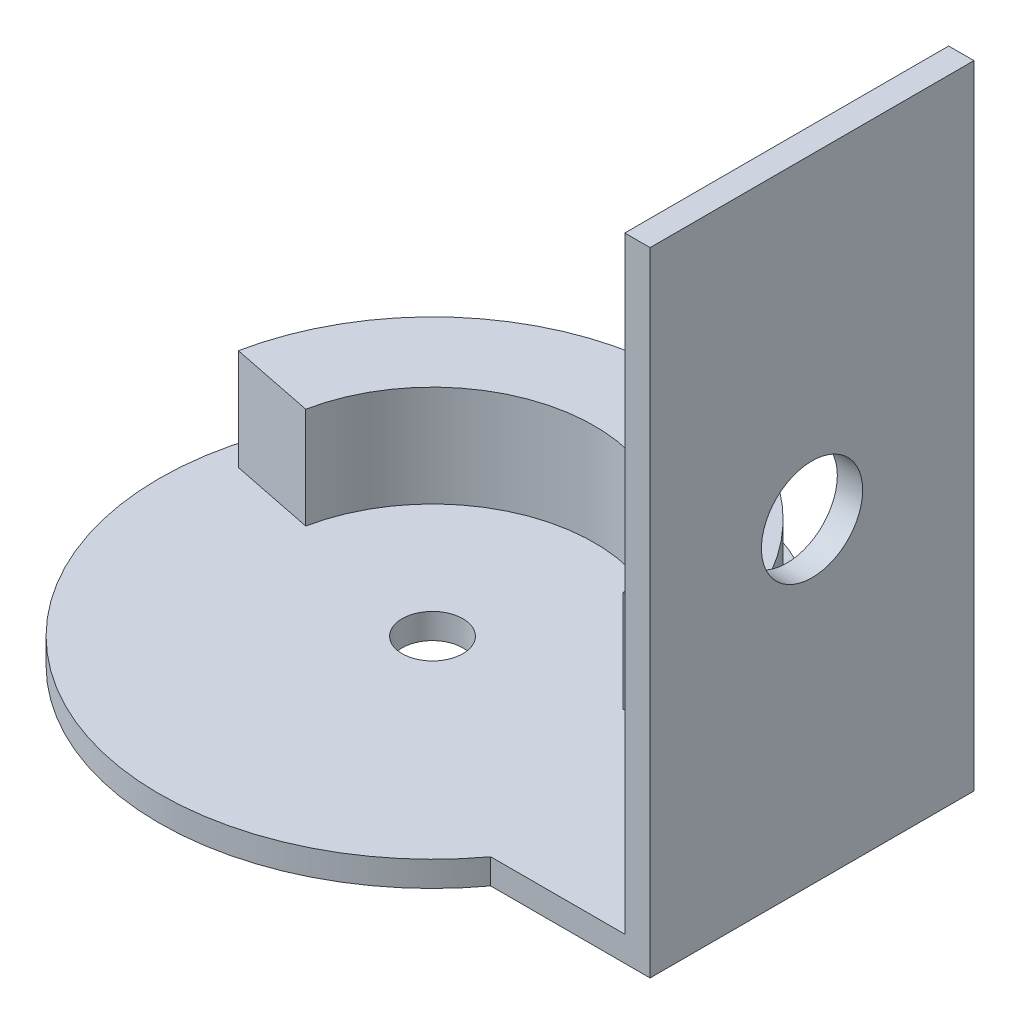
SolidWorks part; units mm, degrees
ref_plane "Front Plane" through (0, 0, 0) normal (0, 0, 1) x (1, 0, 0)
ref_plane "Top Plane" through (0, 0, 0) normal (0, 1, 0) x (1, 0, 0)
ref_plane "Right Plane" through (0, 0, 0) normal (1, 0, 0) x (0, 0, -1)
sketch "Sketch1" plane through (0, 0, 0) normal (0, 1, 0) x (1, 0, 0)
  line L0 (-55, 0) -> (55, 0) construction
  line L1 (-24.0173, 4.8395) -> (-20.7184, 21.2108) construction
  line L2 (-24.0173, 4.8395) -> (-15.6847, 3.1605)
  line L3 (0, -55) -> (0, 55) construction
  line L4 (24.0173, 4.8395) -> (15.6847, 3.1605)
  line L5 (-23.9844, 5) -> (23.9844, 5) construction
  circle A0 centre (0, 0) radius 16 construction
  circle A1 centre (0, 0) radius 24.5 construction
  arc A2 (-24.0173, 4.8395) -> (24.0173, 4.8395) centre (0, 0) cw
  arc A3 (-15.6847, 3.1605) -> (15.6847, 3.1605) centre (0, 0) cw
  point P20 (-19.851, 4)
  dimension "D1" = 32
  dimension "D2" = 49
  dimension "D3" = 1
  dimension "D4" = 5
extrude "Boss-Extrude1" add sketch "Sketch1" along normal blind 10 contours A2 L4 A3 L2
sketch "Sketch2" plane through (0, 0, 0) normal (0, -1, 0) x (1, 0, 0)
  line L1 (37.5, -16) -> (37.5, 16)
  line L3 (21.7486, -16) -> (37.5, -16)
  line L5 (21.7486, 16) -> (37.5, 16)
  line L6 (0, -55) -> (0, 55) construction
  circle A1 centre (0, 0) radius 27 construction
  circle A2 centre (0, 0) radius 3
  arc A3 (0, -27) -> (0, 27) centre (0, 0) cw
  circle A4 centre (0, 0) radius 16 construction
  arc A5 (21.7486, -16) -> (0, -27) centre (0, 0) cw
  arc A6 (0, 27) -> (21.7486, 16) centre (0, 0) cw
  dimension "D1" = 54
  dimension "D2" = 6
  dimension "D3" = 37.5
extrude "Boss-Extrude2" add sketch "Sketch2" along normal blind 2.5
sketch "Sketch4" plane through (0, 0, 0) normal (0, 1, 0) x (1, 0, 0)
  line L0 (37.5, -16) -> (21.7486, -16) construction
  line L1 (37.5, -16) -> (35, -16)
  line L2 (37.5, -16) -> (37.5, 16)
  line L3 (37.5, 16) -> (35, 16)
  line L4 (35, -16) -> (35, 16)
  line L5 (21.7486, 16) -> (37.5, 16) construction
  dimension "D1" = 2.5
  dimension "D2" = 35
extrude "Boss-Extrude3" add sketch "Sketch4" along normal blind 60
sketch "Sketch5" plane through (37.5, 0, 0) normal (1, 0, 0) x (0, 0, -1)
  line L0 (16, 60) -> (-16, -2.5) construction
  line L1 (-16, -2.5) -> (16, -2.5) construction
  line L2 (16, -2.5) -> (-16, 60) construction
  circle A0 centre (0, 28.75) radius 5
  dimension "D1" = 10
extrude "Cut-Extrude1" cut sketch "Sketch5" against normal blind 10
ref_axis "Axis1" through (35, 28.75, 0) along (1, 0, 0)
ref_plane "Plane1" through (0, 28.75, 0) normal (0, 1, 0) x (1, 0, 0)
